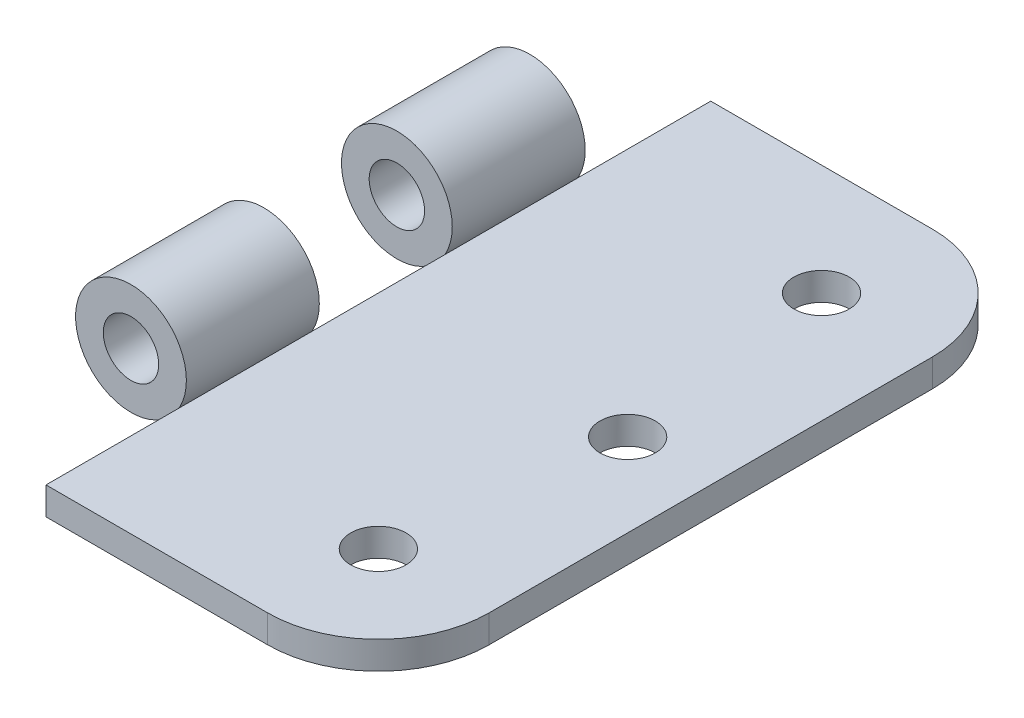
SolidWorks part; units mm, degrees
ref_plane "Front Plane" through (0, 0, 0) normal (0, 0, 1) x (1, 0, 0)
ref_plane "Top Plane" through (0, 0, 0) normal (0, 1, 0) x (1, 0, 0)
ref_plane "Right Plane" through (0, 0, 0) normal (1, 0, 0) x (0, 0, -1)
sketch "Sketch1" plane through (0, 0, 0) normal (0, 1, 0) x (1, 0, 0)
  line L1 (0, 0) -> (38.1, 0)
  line L2 (0, 0) -> (0, 76.2)
  line L3 (0, 76.2) -> (38.1, 76.2)
  line L4 (38.1, 0) -> (38.1, 76.2)
  dimension "D1" = 38.1
  dimension "D2" = 76.2
extrude "Boss-Extrude1" add sketch "Sketch1" along normal blind 3.175
sketch "Sketch2" plane through (0, 3.175, 0) normal (0, 1, 0) x (-1, 0, 0)
  line L0 (-38.1, 0) -> (-38.1, -76.2) construction
  line L1 (-38.1, -38.1) -> (0, -38.1) construction
  line L2 (0, -76.2) -> (0, 0) construction
  circle A0 centre (-25.4, -63.5) radius 3.175
  circle A1 centre (-28.575, -38.1) radius 3.175
  circle A2 centre (-25.4, -12.7) radius 3.175
  dimension "D4" = 6.35
  dimension "D3" = 25.4
  dimension "D1" = 9.525
  dimension "D2" = 12.7
extrude "Cut-Extrude1" cut sketch "Sketch2" against normal up to next
fillet "Fillet1" radius 12.7 2 edges at (38.1, 1.5875, 0) (38.1, 1.5875, -76.2)
sketch "Sketch3" plane through (0, 0, 0) normal (0, 0, 1) x (1, 0, 0)
  line L0 (0, 0) -> (25.4, 0) construction
  circle A0 centre (-5.4993, 6.35) radius 6.35
  circle A1 centre (-5.4993, 6.35) radius 3.175
  dimension "D1" = 12.7
  dimension "D2" = 6.35
extrude "Boss-Extrude2" add sketch "Sketch3" against normal blind 15.24 from offset 15.24 separate body offset against normal yes
extrude "Boss-Extrude3" add sketch "Sketch3<2>" against normal blind 15.24 from offset 45.72 separate body offset against normal yes
sketch "Sketch3<2>" plane through (0, 0, 0) normal (0, 0, 1) x (1, 0, 0) same geometry as "Sketch3"
